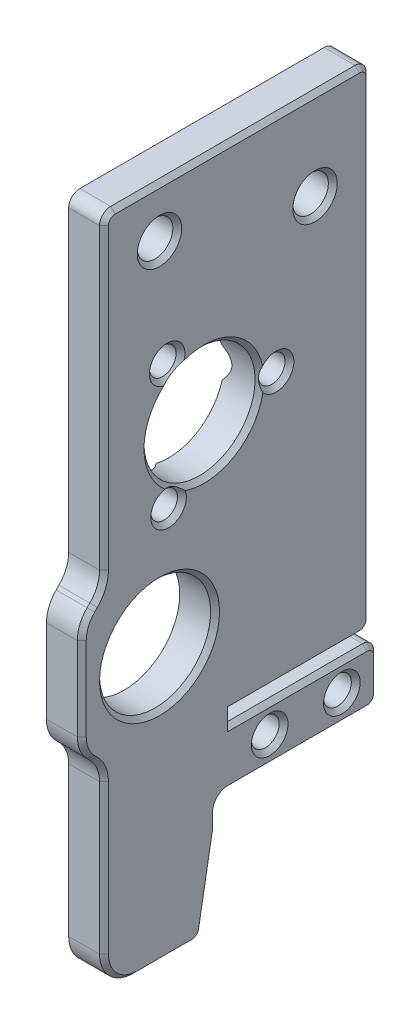
SolidWorks part; units mm, degrees
ref_plane "Front Plane" through (0, 0, 0) normal (0, 0, 1) x (1, 0, 0)
ref_plane "Top Plane" through (0, 0, 0) normal (0, 1, 0) x (1, 0, 0)
ref_plane "Right Plane" through (0, 0, 0) normal (1, 0, 0) x (0, 0, -1)
sketch "Sketch2" plane through (0, 0, 0) normal (1, 0, 0) x (0, 0, -1)
  line L0 (0, 60.81) -> (24, 60.81)
  line L1 (24, 60.81) -> (24, 16.53)
  line L2 (10.17, 0) -> (0, 0)
  line L3 (-2, 19.7) -> (-2, 29.7)
  line L4 (-14.1477, -4) -> (43.3175, -4) construction
  line L14 (0, 31.7) -> (0, 60.81)
  line L16 (0, 17.7) -> (0, 0)
  line L19 (10.17, 0) -> (10.17, 10.38)
  line L20 (10.17, 10.38) -> (24.67, 10.38)
  line L25 (-2, 29.7) -> (0, 31.7)
  line L26 (-2, 19.7) -> (0, 17.7)
  line L28 (5, 29.7) -> (-2, 29.7) construction
  line L29 (5, 19.7) -> (-2, 19.7) construction
  line L31 (11.52, 16.53) -> (11.52, 15.38)
  line L40 (24.67, 15.38) -> (24.67, 10.38)
  line L41 (24.67, 15.38) -> (11.52, 15.38)
  line L42 (11.52, 16.53) -> (24, 16.53)
  circle A1 centre (5, 24.7) radius 5
  circle A2 centre (9, 40.8109) radius 8 construction
  circle A3 centre (9, 40.8109) radius 5
  dimension "D1" = 28.7
  dimension "D2" = 5
  dimension "D4" = 24
  dimension "D6" = 16
  dimension "D7" = 10
  dimension "D3" = 10
  dimension "D10" = 2
  dimension "D9" = 2
  dimension "D11" = 1.15
  dimension "D5" = 16.6
  dimension "D8" = 9
  dimension "D12" = 10.38
  dimension "D13" = 4
  dimension "D14" = 13.15
  dimension "D15" = 1.35
  dimension "D16" = 10.17
  dimension "D17" = 60.81
extrude "Boss-Extrude1" add sketch "Sketch2" against normal blind 3.18 contours L0 L1 L42 L31 L41 L40 L20 L19 L2 L16 L26 L3 L25 L14
extrude "Cut-Extrude2" cut sketch "Sketch2<4>" against normal blind 3.18 flip side to cut
sketch "Sketch2<4>" plane through (0, 0, 0) normal (1, 0, 0) x (0, 0, -1) same geometry as "Sketch2"
fillet "Fillet6" radius 3 5 edges at (-1.59, 17.7, 0) (-1.59, 19.7, 2) (-1.59, 29.7, 2) (-1.59, 31.7, 0) (-1.59, 0, 0)
sketch "Sketch10" plane through (-3.18, 0, 0) normal (-1, 0, 0) x (0, 0, 1)
  line L0 (-15.4996, 40.8823) -> (-5.6884, 46.404) construction
  line L1 (-5.6884, 46.404) -> (-5.812, 35.1463) construction
  line L2 (-5.812, 35.1463) -> (-15.4996, 40.8823) construction
  circle A0 centre (-9, 40.8109) radius 6.5 construction
  circle A1 centre (-5.6884, 46.404) radius 1
  circle A2 centre (-5.812, 35.1463) radius 1
  circle A3 centre (-15.4996, 40.8823) radius 1
  dimension "D1" = 13
  dimension "D2" = 2
hole_wizard "CSK for M2 Flat Head Machine Screw2" positions "Sketch11" profile "Sketch12" countersink size "M2" standard "ANSI Metric" end condition up to next
sketch "Sketch11" plane through (-3.18, 0, 0) normal (-1, 0, 0) x (0, 0, 1)
  point P0 (-5.6884, 46.404)
  point P3 (-15.4996, 40.8823)
  point P6 (-5.812, 35.1463)
sketch "Sketch12" plane through (-3.18, 46.404, -5.6884) normal (0, 1, 0) x (0, 0, 1)
  line L0 (0, 0) -> (0, 3.18)
  line L1 (0, 3.18) -> (1.2, 3.18)
  line L2 (1.2, 3.18) -> (1.2, 1)
  line L3 (1.2, 1) -> (2.2, 0)
  line L5 (2.2, 0) -> (0, 0)
  line L6 (-1.2, 1) -> (-2.2, 0) construction
  line L11 (0, -6.35) -> (0, 107.95) construction
  dimension "Thru Hole Dia." = 2.4
  dimension "Thru Hole Depth" = 3.18
  dimension "Near C'Sink Dia." = 4.4
  dimension "Near C'Sink Angle" = 90
mirror "Mirror1" [suppressed] of bodies 104
delete or keep bodies "Body-Delete/Keep 1" [suppressed] type delete bodies bodies 104
hole_wizard "M3x0.5 Tapped Hole1" positions "Sketch13" profile "Sketch15" tap size "M3x0.5" standard "ANSI Metric"
sketch "Sketch13" plane through (0, 0, 0) normal (1, 0, 0) x (0, 0, -1)
  line L0 (24.67, 15.38) -> (24.67, 10.38) construction
  line L1 (24.67, 15.38) -> (11.52, 15.38) construction
  point P2 (21.42, 12.88)
  point P4 (14.92, 12.88)
  dimension "D1" = 3.25
  dimension "D2" = 6.5
  dimension "D3" = 2.5
sketch "Sketch15" plane through (0, 12.88, -21.42) normal (0, 1, 0) x (0, 0, -1)
  line L0 (0, 0) -> (0, 4.23)
  line L1 (0, 4.23) -> (1.25, 3.4789)
  line L2 (1.25, 3.4789) -> (1.25, 0)
  line L5 (1.25, 0) -> (0, 0)
  line L10 (0, 4.23) -> (-1.25, 3.4789) construction
  line L11 (0, -6.35) -> (0, 107.95) construction
  dimension "Tap Drill Dia." = 2.5
  dimension "Tap Drill Depth" = 4.23
  dimension "Drill Angle" = 118
cosmetic thread "Hole Thread1" parameters "D1"=1.73, "D2"=3
cosmetic thread "Hole Thread2" parameters "D1"=1.73, "D2"=3
chamfer "Chamfer1" distance 8 angle 10 1 edges at (-1.59, 0, -10.17) first distance on face at (-1.59, 5.19, -10.17)
fillet "Fillet7" radius 1 8 edges at (-1.59, 60.81, -24) (-1.59, 60.81, 0) (-1.59, 8, -10.17) (-1.59, 0, -8.7594) (-1.59, 10.38, -10.17) (-1.59, 10.38, -24.67) (-1.59, 15.38, -24.67) (-1.59, 16.53, -24)
sketch "Sketch16" plane through (-3.18, 0, 0) normal (-1, 0, 0) x (0, 0, 1)
  line L0 (-1, 60.81) -> (-23, 60.81) construction
  line L1 (-24, 59.81) -> (-24, 17.53) construction
  line L2 (0, 32.9426) -> (0, 59.81) construction
  circle A0 centre (-19, 52.81) radius 1.6
  circle A1 centre (-5, 56.31) radius 1.6
  dimension "D1" = 3.2
  dimension "D2" = 4.5
  dimension "D3" = 8
  dimension "D4" = 5
  dimension "D5" = 5
extrude "Cut-Extrude3" cut sketch "Sketch16" against normal through all
chamfer "Chamfer2" distance 0.4 angle 45 37 edges at (0, 12.88, -16.17) (0, 15.955, -11.52) (0, 15.38, -17.595) (0, 15.0871, -24.3771) (0, 12.88, -24.67) (0, 10.6729, -24.3771) (0, 10.38, -17.42) (0, 10.0871, -10.4629) (0, 8.7337, -10.17) (0, 8.0003, -10.1662) (0, 4.3701, -9.53) (0, 0.234, -8.5631) (0, 0, -5.4601) (0, 0.8787, -0.8787) (0, 9.7287, 0) (0, 17.6054, 0.2284) (0, 18.7, 1) (0, 19.7946, 1.7716) (0, 24.7, 2) (0, 29.6054, 1.7716) (0, 30.7, 1) (0, 31.7946, 0.2284) (0, 46.3763, 0) (0, 60.5171, -0.2929) (0, 60.81, -12) (0, 60.5171, -23.7071) (0, 38.67, -24) (0, 16.8229, -23.7071) (0, 16.53, -17.26) (0, 40.8109, -14) (0, 24.7, -10) (0, 35.1463, -4.612) (0, 40.8823, -14.2996) (0, 46.404, -4.4884) (0, 12.88, -22.67) (0, 56.31, -3.4) (0, 52.81, -17.4)
equation "\"RollerToBaseplate\"= 28.7mm"
equation "\"SteelShaftDia\"= 10mm"
equation "\"DribblerMotorDia\"= 16mm"
equation "\"DribblerHeight\"= 50mm"
